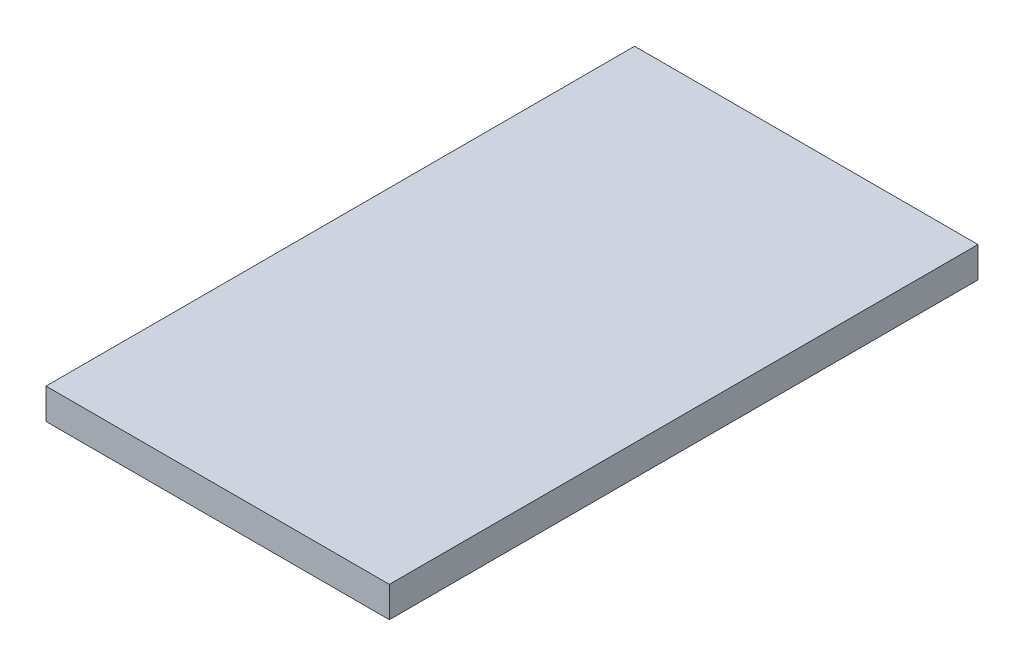
SolidWorks part; units mm, degrees
material "Cedar"
ref_plane "Front Plane" through (0, 0, 0) normal (0, 0, 1) x (1, 0, 0)
ref_plane "Top Plane" through (0, 0, 0) normal (0, 1, 0) x (1, 0, 0)
ref_plane "Right Plane" through (0, 0, 0) normal (1, 0, 0) x (0, 0, -1)
sketch "Sketch1" plane through (0, 0, 0) normal (0, 1, 0) x (1, 0, 0)
  line L1 (-177.8, -304.8) -> (177.8, -304.8)
  line L2 (-177.8, -304.8) -> (-177.8, 304.8)
  line L3 (-177.8, 304.8) -> (177.8, 304.8)
  line L4 (177.8, -304.8) -> (177.8, 304.8)
  line L5 (-177.8, -304.8) -> (177.8, 304.8) construction
  line L6 (-177.8, 304.8) -> (177.8, -304.8) construction
  point P0 (0, 0)
  dimension "D1" = 355.6
  dimension "D2" = 609.6
extrude "Boss-Extrude1" add sketch "Sketch1" along normal blind 31.75
